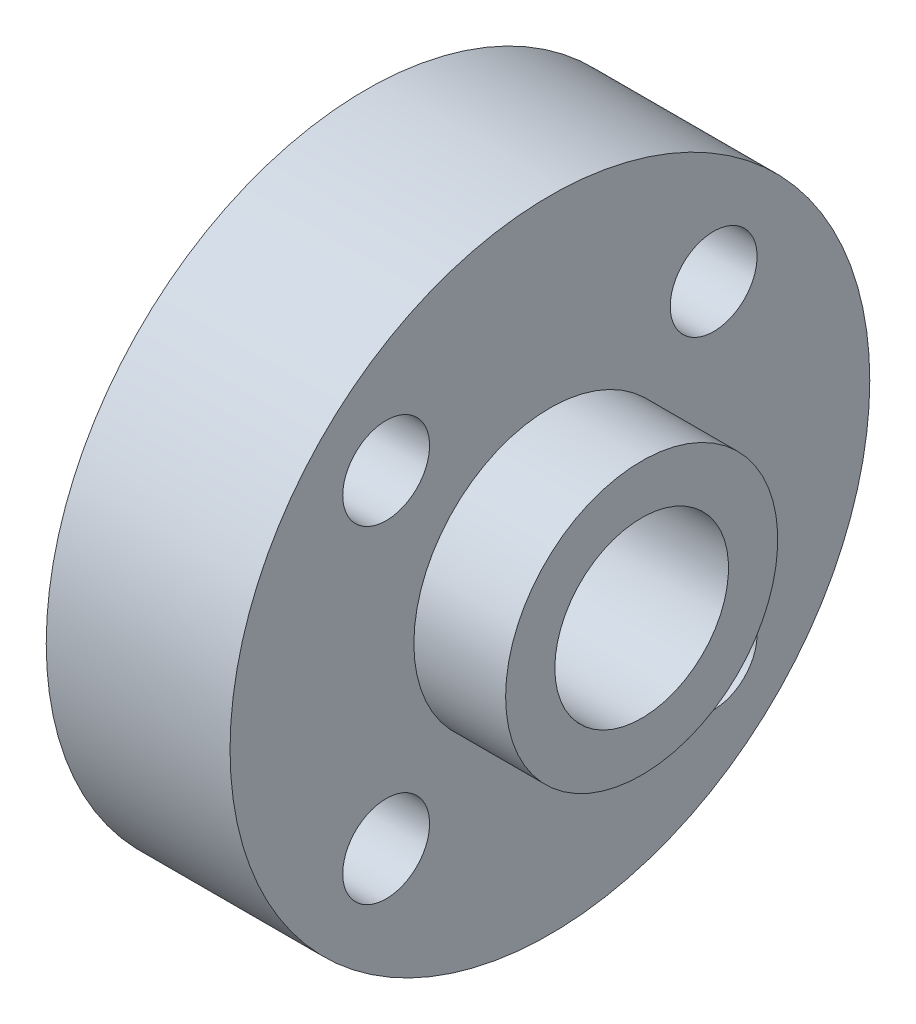
SolidWorks part; units mm, degrees
ref_plane "Plan de face" through (0, 0, 0) normal (0, 0, 1) x (1, 0, 0)
ref_plane "Plan de dessus" through (0, 0, 0) normal (0, 1, 0) x (1, 0, 0)
ref_plane "Plan de droite" through (0, 0, 0) normal (1, 0, 0) x (0, 0, -1)
sketch "Esquisse1" plane through (0, 0, 0) normal (0, 1, 0) x (1, 0, 0)
  line L0 (-53.297, 0) -> (66.3939, 0) construction
  line L1 (-40.2001, 0) -> (-40.2001, 4.7)
  line L2 (-40.2001, 4.7) -> (-37.0201, 4.7)
  line L3 (-37.0201, 4.7) -> (-37.0201, 11.05)
  line L4 (-37.0201, 11.05) -> (-30.6701, 11.05)
  line L5 (-30.6701, 11.05) -> (-30.6701, 4.7)
  line L6 (-30.6701, 4.7) -> (-27.5001, 4.7)
  line L7 (-27.5001, 4.7) -> (-27.5001, 0)
  line L8 (-27.5001, 0) -> (-40.2001, 0)
  dimension "D1" = 3.18
  dimension "D2" = 9.53
  dimension "D3" = 12.7
  dimension "D4" = 4.7
  dimension "D5" = 4.7
  dimension "D6" = 11.05
revolve "Révolution1" add sketch "Esquisse1" angle 360 about L0
sketch "Esquisse2" plane through (-40.2001, 0, 0) normal (-1, 0, 0) x (0, 0, 1)
  circle A0 centre (0, 0) radius 3
  dimension "D1" = 6
extrude "Enlèv. mat.-Extru.1" cut sketch "Esquisse2" against normal through all
sketch "Esquisse3" plane through (-37.0201, 0, 0) normal (-1, 0, 0) x (0, 0, 1)
  line L0 (0, 0) -> (-5.6569, 5.6569) construction
  line L1 (0, -6.985) -> (0, 6.985) construction
  circle A0 centre (-5.6569, 5.6569) radius 1.5
  dimension "D1" = 3
  dimension "D2" = 45
  dimension "D3" = 8
extrude "Enlèv. mat.-Extru.2" cut sketch "Esquisse3" against normal blind 10
pattern_circular "Répétition circulaire1" count 4 every 90 about axis through (-40.2001, 0, 0) along (-1, 0, 0) of "Enlèv. mat.-Extru.2"
sketch "Esquisse5" plane through (0, 0, 0) normal (0, 0, 1) x (1, 0, 0)
  line L2 (-43.9255, 0) -> (-22.3265, 0) construction
  line L4 (-30.6701, -11.05) -> (-30.6701, 11.05) construction
  circle A0 centre (-33.8451, 0) radius 2.5
  dimension "D1" = 5
  dimension "D2" = 0
  dimension "D3" = 3.175
extrude "Enlèv. mat.-Extru.3" cut sketch "Esquisse5" against normal through all contours A0
